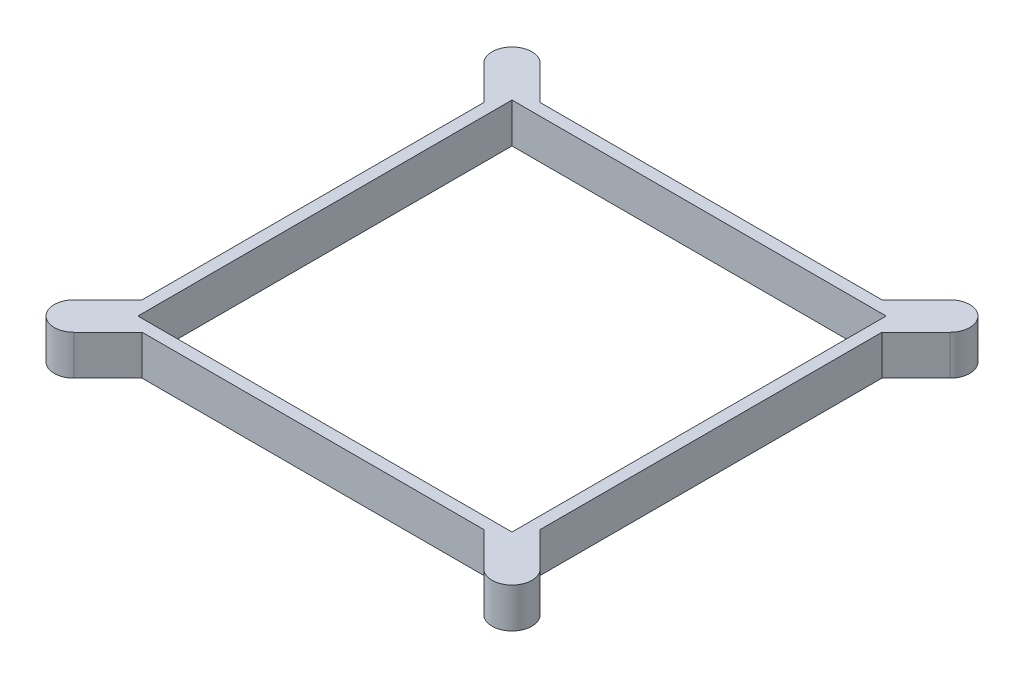
SolidWorks part; units mm, degrees
note: The reader was unsure of these and kept them because the rebuilt part matched: shared geometry of "Sketch2<4>".
ref_plane "Front Plane" through (0, 0, 0) normal (0, 0, 1) x (1, 0, 0)
ref_plane "Top Plane" through (0, 0, 0) normal (0, 1, 0) x (1, 0, 0)
ref_plane "Right Plane" through (0, 0, 0) normal (1, 0, 0) x (0, 0, -1)
sketch "Sketch1" plane through (0, 0, 0) normal (0, 1, 0) x (1, 0, 0)
  line L1 (0, 0) -> (200, 0)
  line L2 (0, 0) -> (0, 200)
  line L3 (0, 200) -> (200, 200)
  line L4 (200, 0) -> (200, 200)
  dimension "D1" = 200
  dimension "D2" = 200
extrude "Boss-Extrude1" add sketch "Sketch1" along normal blind 20
sketch "Sketch2" plane through (0, 0, 0) normal (0, -1, 0) x (1, 0, 0)
  line L0 (0, -14.1421) -> (-17.0876, 2.9455)
  line L2 (-2.9455, 17.0876) -> (14.1421, 0)
  line L4 (0, 0) -> (200, -200) construction
  line L5 (200, -200) -> (0, -200) construction
  line L6 (200, 0) -> (200, -200) construction
  line L7 (-10.0166, 10.0166) -> (0, 0) construction
  line L8 (0, -200) -> (200, 0) construction
  line L9 (0, 0) -> (200, 0) construction
  line L10 (0, -200) -> (0, 0) construction
  line L11 (0, -14.1421) -> (0, 0)
  line L12 (0, 0) -> (14.1421, 0)
  line L13 (14.1421, 0) -> (13.2949, 0.1447)
  line L14 (0, -14.1421) -> (-0.1447, -13.2949)
  line L15 (0, 0) -> (0, -14.1421)
  line L16 (14.1421, 0) -> (0, 0)
  line L17 (-17.0876, 2.9455) -> (0, -14.1421)
  line L18 (14.1421, 0) -> (-2.9455, 17.0876)
  arc A0 (-17.0876, 2.9455) -> (-2.9455, 17.0876) centre (-10.0166, 10.0166) cw
  circle A1 centre (-10.0166, 10.0166) radius 3.7971
  circle A2 centre (-3.4154, 3.4154) radius 3.7971
  dimension "D1" = 10
  dimension "D2" = 7.5942
extrude "Boss-Extrude2" add sketch "Sketch2" against normal up to surface (20 mm away) up to face at (100, 20, -100)
extrude "Cut-Extrude2" cut sketch "Sketch2<4>" against normal blind 10 contours A1 | A2
sketch "Sketch2<4>" plane through (0, 0, 0) normal (0, -1, 0) x (1, 0, 0) same geometry as "Sketch2"
ref_plane "Plane1" through (0, 0, -100) normal (0, 0, -1) x (-1, 0, 0)
ref_plane "Plane2" through (100, 0, 0) normal (1, 0, 0) x (0, 0, -1)
mirror "Mirror3" about plane through (100, 0, 0) normal (1, 0, 0) of "Cut-Extrude2", "Boss-Extrude2"
mirror "Mirror4" about plane through (0, 0, -100) normal (0, 0, -1) of "Mirror3", "Boss-Extrude2", "Cut-Extrude2"
sketch "Sketch3" plane through (0, 0, 0) normal (0, -1, 0) x (1, 0, 0)
  line L0 (100, -11) -> (100, 11) construction
  line L1 (6, -194) -> (194, -194)
  line L2 (6, -194) -> (6, -6)
  line L3 (6, -6) -> (194, -6)
  line L4 (194, -194) -> (194, -6)
  line L5 (6, -194) -> (194, -6) construction
  line L6 (6, -6) -> (194, -194) construction
  line L7 (-11, -100) -> (11, -100) construction
  line L8 (14.1421, 0) -> (185.8579, 0) construction
  point P0 (100, -100)
  dimension "D1" = 6
extrude "Cut-Extrude1" cut sketch "Sketch3" against normal through all
